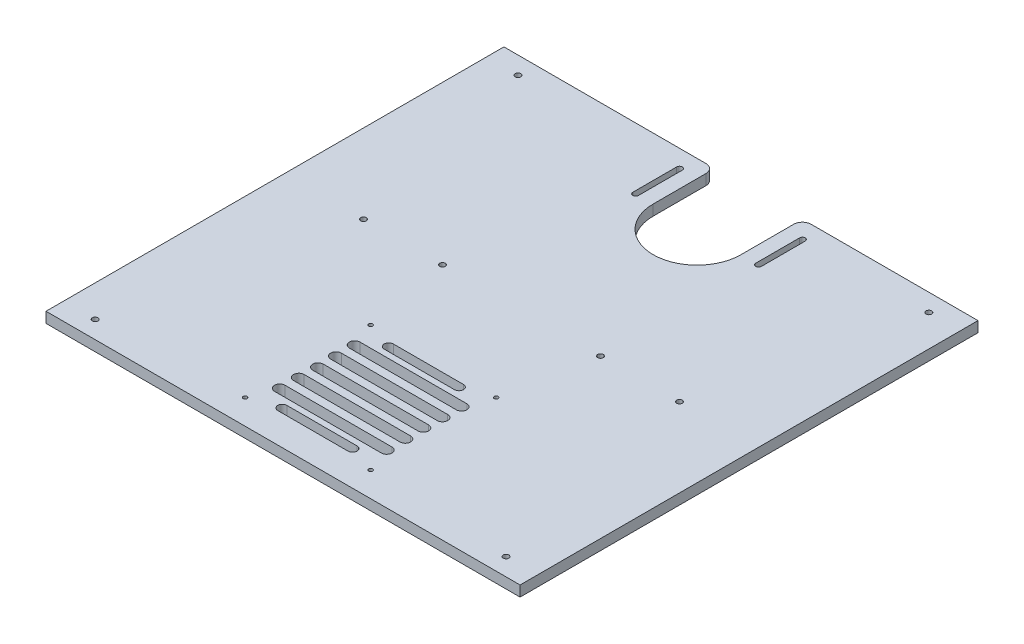
SolidWorks part; units mm, degrees
ref_plane "Front Plane" through (0, 0, 0) normal (0, 0, 1) x (1, 0, 0)
ref_plane "Top Plane" through (0, 0, 0) normal (0, 1, 0) x (1, 0, 0)
ref_plane "Right Plane" through (0, 0, 0) normal (1, 0, 0) x (0, 0, -1)
sketch "Sketch1" plane through (0, 0, 0) normal (0, 1, 0) x (1, 0, 0)
  line L0 (-145, 120) -> (125, 120)
  line L1 (-145, 120) -> (-145, -100.8)
  line L3 (125, 120) -> (125, -100.8)
  line L4 (0, 0) -> (0, 120) construction
  line L7 (-145, -100.8) -> (-145, -140.8)
  line L8 (-145, -140.8) -> (125, -140.8)
  line L9 (125, -100.8) -> (125, -140.8)
  circle A0 centre (-100, -5) radius 1.6
  circle A2 centre (80, -5) radius 1.6
  circle A3 centre (-55, -5) radius 1.6
  circle A4 centre (35, -5) radius 1.6
  circle A6 centre (-55, -5) radius 1.125 construction
  dimension "D1" = 3.2
  dimension "D2" = 40
extrude "Boss-Extrude1" add sketch "Sketch1" along normal blind 6
sketch "Sketch3" plane through (0, 6, 0) normal (0, 1, 0) x (1, 0, 0)
  line L3 (0, 120) -> (0, 0) construction
  line L4 (125, 120) -> (-145, 120) construction
  line L5 (-25, 85) -> (-25, 120)
  line L60 (25, 85) -> (25, 120)
  line L61 (25, 120) -> (-25, 120)
  arc A0 (-25, 85) -> (25, 85) centre (0, 85) ccw
  dimension "D1" = 25
  dimension "D2" = 35
extrude "Cut-Extrude1" cut sketch "Sketch3" against normal through all both and the other way through all
sketch "Sketch4" plane through (0, 0, 0) normal (0, -1, 0) x (1, 0, 0)
  circle A0 centre (107, -110) radius 1.6
  circle A1 centre (-127, -110) radius 1.6
  circle A2 centre (107, 130.8) radius 1.6
  circle A3 centre (-127, 130.8) radius 1.6
extrude "Cut-Extrude2" cut sketch "Sketch4" against normal blind 10
sketch "Sketch5" plane through (0, 6, 0) normal (0, 1, 0) x (1, 0, 0)
  line L0 (25, 85) -> (25, 120) construction
  line L1 (-25, 120) -> (-25, 85) construction
  line L2 (25, 85) -> (25, 120) construction
  line L3 (-25, 120) -> (-25, 85) construction
  line L4 (-25, 120) -> (25, 120) construction
  line L5 (-35, 120) -> (-35, 85) construction
  line L6 (-25, 120) -> (-145, 120) construction
  line L7 (-35, 110) -> (-35, 85) construction
  line L8 (-33.4, 110) -> (-33.4, 85)
  line L9 (-36.6, 110) -> (-36.6, 85)
  line L10 (0, 120) -> (0, 85) construction
  line L11 (35, 120) -> (35, 85) construction
  line L12 (35, 110) -> (35, 85) construction
  line L13 (33.4, 110) -> (33.4, 85)
  line L14 (36.6, 110) -> (36.6, 85)
  arc A0 (-33.4, 110) -> (-36.6, 110) centre (-35, 110) ccw
  arc A1 (-36.6, 85) -> (-33.4, 85) centre (-35, 85) ccw
  arc A2 (33.4, 110) -> (36.6, 110) centre (35, 110) cw
  arc A3 (36.6, 85) -> (33.4, 85) centre (35, 85) cw
  point P8 (-35, 110)
  point P12 (-35, 97.5)
  point P21 (35, 97.5)
  dimension "D3" = 1.6
  dimension "D2" = 10
extrude "Cut-Extrude3" cut sketch "Sketch5" against normal blind 10
fillet "Fillet1" radius 5 2 edges at (25, 3, -120) (-25, 3, -120)
sketch "Sketch6" plane through (0, 6, 0) normal (0, 1, 0) x (1, 0, 0)
  line L0 (-10, -140.8) -> (-10, -40.9987) construction
  line L1 (-145, -140.8) -> (125, -140.8) construction
  line L2 (-40, -90.8994) -> (20, -90.8994) construction
  line L3 (-45.75, -55.1494) -> (25.75, -55.1494) construction
  line L4 (-45.75, -55.1494) -> (-45.75, -126.6494) construction
  line L5 (-45.75, -126.6494) -> (25.75, -126.6494) construction
  line L6 (25.75, -55.1494) -> (25.75, -126.6494) construction
  line L7 (-45.75, -55.1494) -> (25.75, -126.6494) construction
  line L8 (-45.75, -126.6494) -> (25.75, -55.1494) construction
  line L9 (-40, -87.8994) -> (20, -87.8994)
  line L10 (-40, -93.8994) -> (20, -93.8994)
  line L11 (-40.3168, -80.3259) -> (20.3168, -80.3259) construction
  line L12 (-40.3168, -77.3259) -> (20.3168, -77.3259)
  line L13 (-40.3168, -83.3259) -> (20.3168, -83.3259)
  line L14 (-40.436, -69.5711) -> (20.436, -69.5711) construction
  line L15 (-40.436, -66.5711) -> (20.436, -66.5711)
  line L16 (-40.436, -72.5711) -> (20.436, -72.5711)
  line L17 (-30, -60.5923) -> (10, -60.5923) construction
  line L18 (-30, -58.0215) -> (10, -58.0215)
  line L19 (-30, -63.1632) -> (10, -63.1632)
  line L20 (-74.1524, -90.8994) -> (67.5301, -90.8994) construction
  line L21 (-45.75, -126.6494) -> (25.75, -126.6494) construction
  line L22 (-30, -121.2064) -> (10, -121.2064) construction
  line L23 (-30, -123.7773) -> (10, -123.7773)
  line L24 (-30, -118.6356) -> (10, -118.6356)
  line L25 (-40.436, -112.2277) -> (20.436, -112.2277) construction
  line L26 (-40.436, -115.2277) -> (20.436, -115.2277)
  line L27 (-40.436, -109.2277) -> (20.436, -109.2277)
  line L28 (-40.3168, -101.4728) -> (20.3168, -101.4728) construction
  line L29 (-40.3168, -104.4728) -> (20.3168, -104.4728)
  line L30 (-40.3168, -98.4728) -> (20.3168, -98.4728)
  circle A0 centre (25.75, -55.1494) radius 1.125
  circle A1 centre (-45.75, -55.1494) radius 1.125
  circle A2 centre (-45.75, -126.6494) radius 1.125
  circle A3 centre (25.75, -126.6494) radius 1.125
  arc A4 (-40, -87.8994) -> (-40, -93.8994) centre (-40, -90.8994) ccw
  arc A5 (20, -93.8994) -> (20, -87.8994) centre (20, -90.8994) ccw
  arc A6 (-40.3168, -77.3259) -> (-40.3168, -83.3259) centre (-40.3168, -80.3259) ccw
  arc A7 (20.3168, -83.3259) -> (20.3168, -77.3259) centre (20.3168, -80.3259) ccw
  arc A8 (-40.436, -66.5711) -> (-40.436, -72.5711) centre (-40.436, -69.5711) ccw
  arc A9 (20.436, -72.5711) -> (20.436, -66.5711) centre (20.436, -69.5711) ccw
  arc A10 (-30, -58.0215) -> (-30, -63.1632) centre (-30, -60.5923) ccw
  arc A11 (10, -63.1632) -> (10, -58.0215) centre (10, -60.5923) ccw
  arc A12 (-30, -123.7773) -> (-30, -118.6356) centre (-30, -121.2064) cw
  arc A13 (10, -118.6356) -> (10, -123.7773) centre (10, -121.2064) cw
  arc A14 (-40.436, -115.2277) -> (-40.436, -109.2277) centre (-40.436, -112.2277) cw
  arc A15 (20.436, -109.2277) -> (20.436, -115.2277) centre (20.436, -112.2277) cw
  arc A16 (-40.3168, -104.4728) -> (-40.3168, -98.4728) centre (-40.3168, -101.4728) cw
  arc A17 (20.3168, -98.4728) -> (20.3168, -104.4728) centre (20.3168, -101.4728) cw
  point P4 (-10, -80.3259)
  point P6 (-10, -90.8994)
  point P16 (-10, -90.8994)
  point P23 (-10, -80.3259)
  point P28 (-10, -69.5711)
  point P31 (-10, -69.5711)
  point P36 (-10, -60.5923)
  point P47 (-10, -121.2064)
  point P54 (-10, -112.2277)
  point P61 (-10, -101.4728)
  dimension "D3" = 2.25
  dimension "D4" = 2.25
  dimension "D5" = 2.25
  dimension "D6" = 2.25
  dimension "D8" = 3
  dimension "D9" = 3
  dimension "D10" = 3
  dimension "D1" = 71.5
  dimension "D2" = 71.5
  dimension "D7" = 60
  dimension "D11" = 40
extrude "Cut-Extrude4" cut sketch "Sketch6" against normal blind 10
